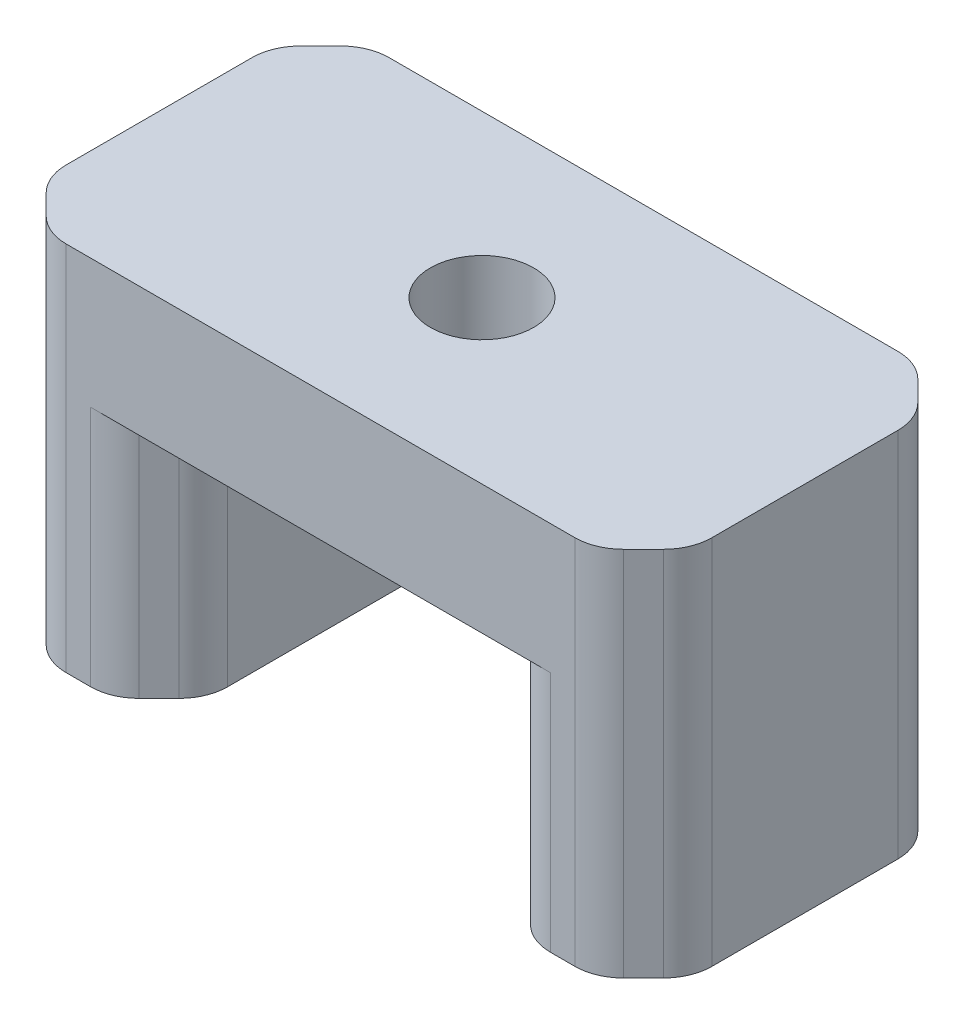
SolidWorks part; units mm, degrees
ref_plane "Plan de face" through (0, 0, 0) normal (0, 0, 1) x (1, 0, 0)
ref_plane "Plan de dessus" through (0, 0, 0) normal (0, 1, 0) x (1, 0, 0)
ref_plane "Plan de droite" through (0, 0, 0) normal (1, 0, 0) x (0, 0, -1)
sketch "Esquisse1" plane through (0, 0, 0) normal (0, 1, 0) x (1, 0, 0)
  line L0 (-20, 10) -> (-20, -10)
  line L1 (-20, 10) -> (-10, 10)
  line L2 (10, 0) -> (-10, 0) construction
  line L3 (-10, -10) -> (-20, -10)
  line L4 (-10, -10) -> (-10, 10)
  line L5 (-10, 10) -> (-20, 10)
  line L7 (-20, -10) -> (-10, -10)
  line L8 (-10, -10) -> (-10, 10)
  line L15 (0, -55) -> (0, 55) construction
  line L16 (10, -10) -> (10, 10)
  line L17 (20, -10) -> (10, -10)
  line L18 (10, 10) -> (20, 10)
  line L19 (10, -10) -> (10, 10)
  line L20 (10, -10) -> (20, -10)
  line L21 (20, 10) -> (10, 10)
  line L22 (20, 10) -> (20, -10)
  line L23 (-15, 0) -> (-10, 0) construction
  circle A0 centre (-15, 0) radius 2.75
  circle A2 centre (15, 0) radius 2.75
  circle A3 centre (-15, 0) radius 3.5
  circle A4 centre (15, 0) radius 3.5
  point P8 (0, 0)
  dimension "D1" = 20
  dimension "D5" = 5.5
  dimension "D7" = 5.5
  dimension "D2" = 10
  dimension "D3" = 10
  dimension "D4" = 5
  dimension "D6" = 15
extrude "Boss.-Extru.1" add sketch "Esquisse1" along normal blind 15 contours L3 L4 L1 L0 A0 | L22 L18 L16 L17 A2 | A2 | A0 | A3 A0 | A4 A2 region at (-15, 0, -9.7764) region at (10.2236, 0, 0) region at (-15, 0, 0) region at (15, 0, 0) region at (-18.401, 0, 0) region at (11.599, 0, 0)
sketch "Esquisse3" plane through (0, 15, 0) normal (0, 1, 0) x (1, 0, 0)
  line L0 (-20, -10) -> (20, -10)
  line L1 (20, -10) -> (20, 10)
  line L3 (20, 10) -> (-20, 10)
  line L4 (-20, 10) -> (-20, -10)
  line M1 (-20, -10) -> (-10, -10)
  line M2 (-10, -10) -> (-10, 10)
  line M3 (-10, 10) -> (-20, 10)
  line M4 (-20, 10) -> (-20, -10)
extrude "Boss.-Extru.2" add sketch "Esquisse3" along normal blind 8 contours M4 M1 M2 M3 | L1 L3 L0 M2 | L4 L0 L1 L3 region at (-15, 15, 0) region at (5, 15, 0)
sketch "Esquisse4" plane through (0, 23, 0) normal (0, 1, 0) x (1, 0, 0)
  circle A0 centre (0, 0) radius 3.2
extrude "Enlèv. mat.-Extru.1" cut sketch "Esquisse4" against normal blind 10
extrude "Enlèv. mat.-Extru.3" cut sketch "Esquisse1<3>" along normal blind 7 contours A0 | A2 region at (-15, 0, 0) region at (15, 0, 0)
sketch "Esquisse1<3>" plane through (0, 0, 0) normal (0, 1, 0) x (1, 0, 0) same geometry as "Esquisse1"
extrude "Enlèv. mat.-Extru.4" cut sketch "Esquisse1<4>" along normal blind 1 contours A3 A0 | A4 A2 region at (-18.401, 0, 0) region at (11.599, 0, 0)
sketch "Esquisse1<4>" plane through (0, 0, 0) normal (0, 1, 0) x (1, 0, 0) same geometry as "Esquisse1"
chamfer "Chanfrein1" distance 3 angle 45 8 edges at (10, 7.5, -10) (20, 11.5, -10) (10, 7.5, 10) (-10, 7.5, -10) (-10, 7.5, 10) (20, 11.5, 10) (-20, 11.5, -10) (-20, 11.5, 10)
fillet "Congé1" radius 3 16 edges at (-10, 7.5, -7) (-13, 7.5, -10) (10, 7.5, -7) (13, 7.5, -10) (13, 7.5, 10) (17, 11.5, 10) (20, 11.5, 7) (20, 11.5, -7) (17, 11.5, -10) (-17, 11.5, -10) (-20, 11.5, -7) (-20, 11.5, 7) (-17, 11.5, 10) (-10, 7.5, 7) (-13, 7.5, 10) (10, 7.5, 7)
